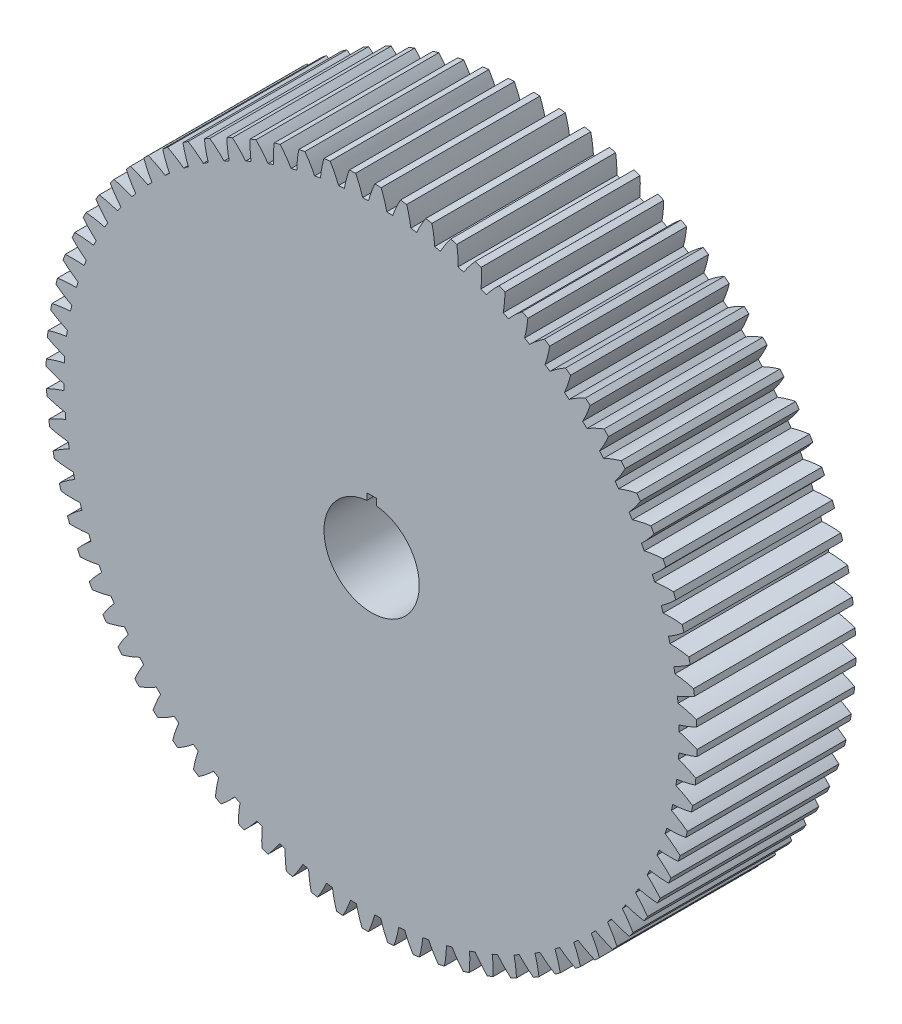
SolidWorks part; units mm, degrees
ref_plane "前视基准面" through (0, 0, 0) normal (0, 0, 1) x (1, 0, 0)
ref_plane "上视基准面" through (0, 0, 0) normal (0, 1, 0) x (1, 0, 0)
ref_plane "右视基准面" through (0, 0, 0) normal (1, 0, 0) x (0, 0, -1)
other "Configuration Table"
sketch "草图1" plane through (0, 0, 0) normal (0, 0, 1) x (1, 0, 0)
  circle A0 centre (0, 0) radius 96.875
  dimension "D1" = 193.75
extrude "凸台-拉伸1" add sketch "草图1" along normal blind 50
sketch "草图2" plane through (0, 0, 50) normal (0, 0, 1) x (1, 0, 0)
  line L0 (0, 0) -> (0, 157.3243) construction
  line L1 (0, 0) -> (55.8778, 153.5229) construction
  line L2 (0, 0) -> (3.4836, 177.3944) construction
  line L3 (0, 100) -> (32.1394, 88.3022) construction
  circle A0 centre (0, 0) radius 100 construction
  arc A1 (3.0036, 102.456) -> (1.0211, 102.4949) centre (0, 0) ccw
  circle A2 centre (0, 0) radius 96.875 construction
  arc A3 (4.7744, 96.7573) -> (-0.9721, 96.8701) centre (0, 0) ccw
  arc A4 (1.0211, 102.4949) -> (-0.9721, 96.8701) centre (32.1394, 88.3022) ccw
  arc A5 (3.0036, 102.456) -> (4.7744, 96.7573) centre (-28.6479, 89.4959) cw
  dimension "D1" = 200
  dimension "D2" = 205
  dimension "D3" = 20
  dimension "D4" = 1.125
extrude "凸台-拉伸2" add sketch "草图2" against normal blind 50
pattern_circular "阵列(圆周)1" count 80 over 360 about axis through (0, 0, 50) along (0, 0, 1) of "凸台-拉伸2"
sketch "草图3" plane through (0, 0, 50) normal (0, 0, 1) x (1, 0, 0)
  line L1 (-1.5, 0) -> (1.5, 0)
  line L2 (-1.5, 0) -> (-1.5, 17)
  line L3 (-1.5, 17) -> (1.5, 17)
  line L4 (1.5, 0) -> (1.5, 17)
  circle A0 centre (0, 0) radius 15
  point P7 (0, 0)
  dimension "D1" = 30
  dimension "D2" = 3
  dimension "D3" = 17
extrude "切除-拉伸1" cut sketch "草图3" against normal through all contours L2 A0 L4 L1 | A0 L4 L3 L2 | L4 A0 L2 L1 region at (0, 7.4875, 50) region at (0, -0.5082, 50) region at (0, 15.9874, 50)
